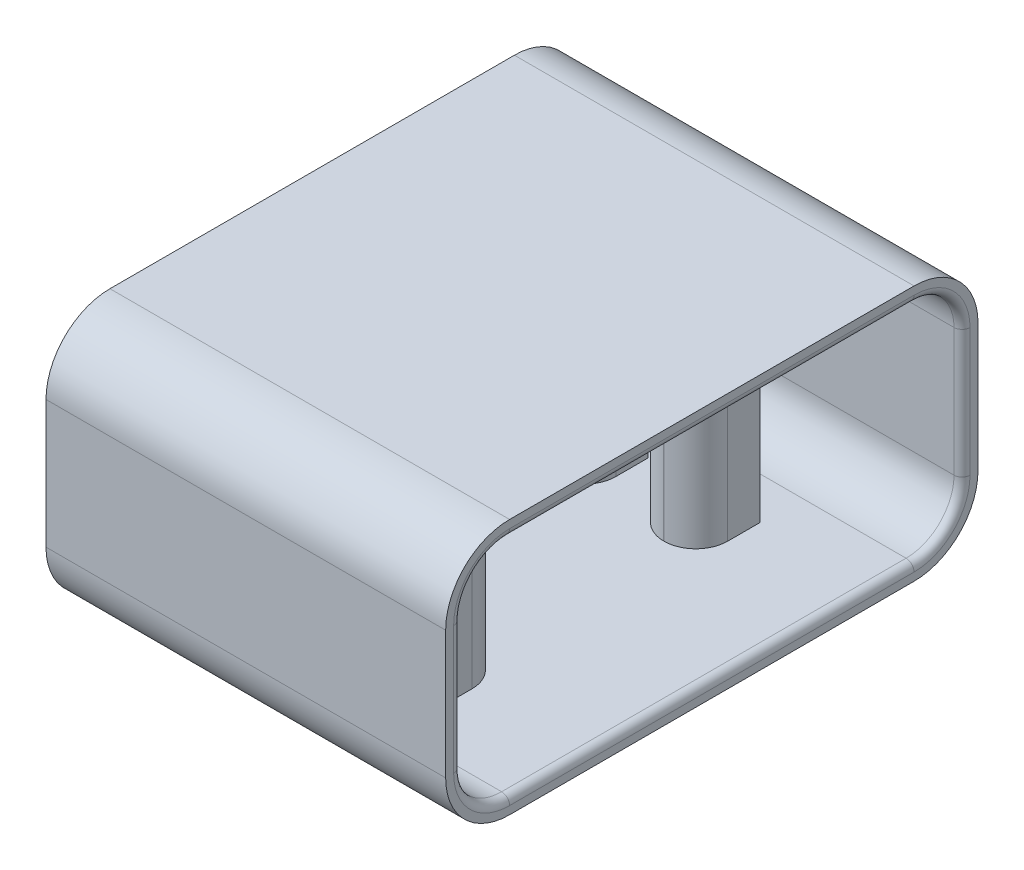
SolidWorks part; units mm, degrees
ref_plane "Front" through (0, 0, 0) normal (0, 0, 1) x (1, 0, 0)
ref_plane "Top" through (0, 0, 0) normal (0, 1, 0) x (1, 0, 0)
ref_plane "Right" through (0, 0, 0) normal (1, 0, 0) x (0, 0, -1)
sketch "Sketch2path" plane through (0, 0, 0) normal (0, 0, 1) x (1, 0, 0)
  line L1 (0, 0) -> (25, 0)
  dimension "D1" = 25
sketch "Sketch3" plane through (0, 0, 0) normal (1, 0, 0) x (0, 0, -1)
  line L0 (0, 8) -> (0, -8) construction
  line L1 (12.65, 8) -> (-12.65, 8)
  line L2 (12.65, -8) -> (-12.65, -8)
  line L3 (16.65, 4) -> (16.65, -4)
  line L4 (-16.65, 4) -> (-16.65, -4)
  line L5 (-15.65, 4) -> (-15.65, -4)
  line L6 (0, 91.8161) -> (0, -91.8161) construction
  line L7 (12.65, -7) -> (-12.65, -7)
  line L8 (15.65, 4) -> (15.65, -4)
  line L9 (12.65, 7) -> (-12.65, 7)
  arc A0 (16.65, -4) -> (12.65, -8) centre (12.65, -4) cw
  arc A1 (12.65, 8) -> (16.65, 4) centre (12.65, 4) cw
  arc A2 (-12.65, 8) -> (-16.65, 4) centre (-12.65, 4) ccw
  arc A3 (-16.65, -4) -> (-12.65, -8) centre (-12.65, -4) ccw
  arc A4 (-12.65, 7) -> (-15.65, 4) centre (-12.65, 4) ccw
  arc A5 (-15.65, -4) -> (-12.65, -7) centre (-12.65, -4) ccw
  arc A6 (15.65, -4) -> (12.65, -7) centre (12.65, -4) cw
  arc A7 (12.65, 7) -> (15.65, 4) centre (12.65, 4) cw
  dimension "D1" = 1
  dimension "D2" = 4
  dimension "D3" = 15.65
  dimension "D4" = 7
  dimension "D5" = 7
sweep "Sweep1" add profiles "Sketch3" path "Sketch2path"
ref_point "Point1"
ref_point "Point2"
ref_axis "os podluzna" through (0, 0, 0) along (1, 0, 0)
ref_plane "Plane4 polowki" through (0, 0, 0) normal (0, 0, 1) x (1, 0, 0)
fillet "Fillet1" radius 0.5 16 edges at (25, -6.1213, 14.7713) (25, 0, 15.65) (25, 6.1213, 14.7713) (25, 7, 0) (25, 6.1213, -14.7713) (25, 0, -15.65) (25, -6.1213, -14.7713) (0, -6.1213, 14.7713) (0, 0, 15.65) (0, 6.1213, 14.7713) (0, 7, 0) (0, 6.1213, -14.7713) (0, 0, -15.65) (0, -6.1213, -14.7713) (25, -7, 0) (0, -7, 0)
sketch "Sketch13" plane through (0, 0, 0) normal (0, 1, 0) x (1, 0, 0)
  line L1 (15.99, -6) -> (16.01, -6)
  line L2 (14, -7.99) -> (14, -10)
  line L3 (14, -10) -> (18, -10)
  line L4 (18, -7.99) -> (18, -10)
  arc A0 (18, -7.99) -> (16.01, -6) centre (16.01, -7.99) ccw
  arc A1 (15.99, -6) -> (14, -7.99) centre (15.99, -7.99) ccw
  point P8 (18, -6)
  point P11 (14, -6)
  dimension "D4" = 6
  dimension "D1" = 1.99
  dimension "D2" = 14
  dimension "D3" = 18
  dimension "D5" = 10
extrude "Boss-Extrude6" add sketch "Sketch13" along normal up to next and the other way up to next
ref_plane "Plane2" through (12.5, 0, 0) normal (1, 0, 0) x (0, 0, -1)
mirror "Mirror1" about plane through (12.5, 0, 0) normal (1, 0, 0) of "Boss-Extrude6"
mirror "Mirror2" about plane through (0, 0, 0) normal (0, 0, 1) of "Mirror1"
